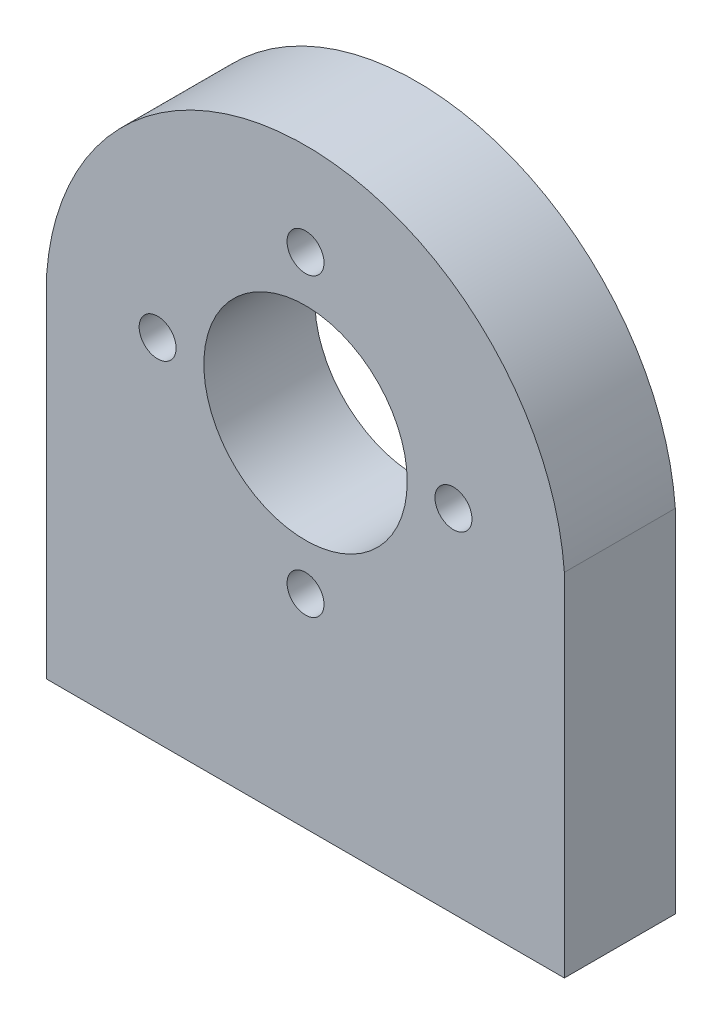
SolidWorks part; units mm, degrees
ref_plane "Front" through (0, 0, 0) normal (0, 0, 1) x (1, 0, 0)
ref_plane "Top" through (0, 0, 0) normal (0, 1, 0) x (1, 0, 0)
ref_plane "Right" through (0, 0, 0) normal (1, 0, 0) x (0, 0, -1)
sketch "Esquisse1" plane through (0, 0, 0) normal (0, 0, 1) x (1, 0, 0)
  line L1 (0, 0) -> (28, 0)
  line L2 (0, 0) -> (0, 32)
  line L3 (0, 32) -> (28, 32)
  line L4 (28, 0) -> (28, 32)
  dimension "D1" = 28
  dimension "D2" = 32
extrude "Boss.-Extru.1" add sketch "Esquisse1" along normal blind 6
sketch "Esquisse2" plane through (0, 0, 0) normal (0, -1, 0) x (1, 0, 0)
  line L0 (0, 3) -> (24.8385, 3) construction
  line L1 (0, 6) -> (0, 0) construction
  line L2 (14, 0) -> (14, 4.923) construction
  line L3 (0, 0) -> (28, 0) construction
  circle A0 centre (6, 3) radius 1.25
  circle A1 centre (22, 3) radius 1.25
  dimension "D1" = 16
  dimension "D2" = 2.5
extrude "Enlèv. mat.-Extru.1" cut sketch "Esquisse2" against normal blind 10
sketch "Esquisse3" plane through (0, 0, 6) normal (0, 0, 1) x (1, 0, 0)
  line L0 (14, 0) -> (14, 19) construction
  line L1 (0, 0) -> (28, 0) construction
  circle A0 centre (14, 19) radius 5.5
  dimension "D1" = 11
  dimension "D2" = 19
extrude "Enlèv. mat.-Extru.2" cut sketch "Esquisse3" against normal through all
sketch "Esquisse4" plane through (0, 0, 6) normal (0, 0, 1) x (1, 0, 0)
  line L0 (14, 19) -> (14, 11) construction
  circle A0 centre (14, 11) radius 1
  circle A1 centre (6, 19) radius 1
  circle A2 centre (14, 27) radius 1
  circle A3 centre (22, 19) radius 1
  point P13 (14, 19)
  dimension "D1" = 2
  dimension "D2" = 8
  dimension "D3" = 4
extrude "Enlèv. mat.-Extru.4" cut sketch "Esquisse4" against normal through all
sketch "Esquisse5" plane through (0, 0, 6) normal (0, 0, 1) x (1, 0, 0)
  line L0 (0, 32) -> (0, 0) construction
  line L1 (28, 0) -> (28, 32) construction
  line L2 (14, 32) -> (28, 32) construction
  line L3 (0, 19) -> (28, 19) construction
  line L4 (0, 19) -> (14, 19) construction
  line L5 (0, 19) -> (0, 33)
  line L6 (0, 33) -> (28, 33)
  line L7 (28, 33) -> (28, 19)
  arc A0 (0, 19) -> (28, 19) centre (14, 17.9615) cw
  dimension "D1" = 1
extrude "Enlèv. mat.-Extru.5" cut sketch "Esquisse5" against normal through all
